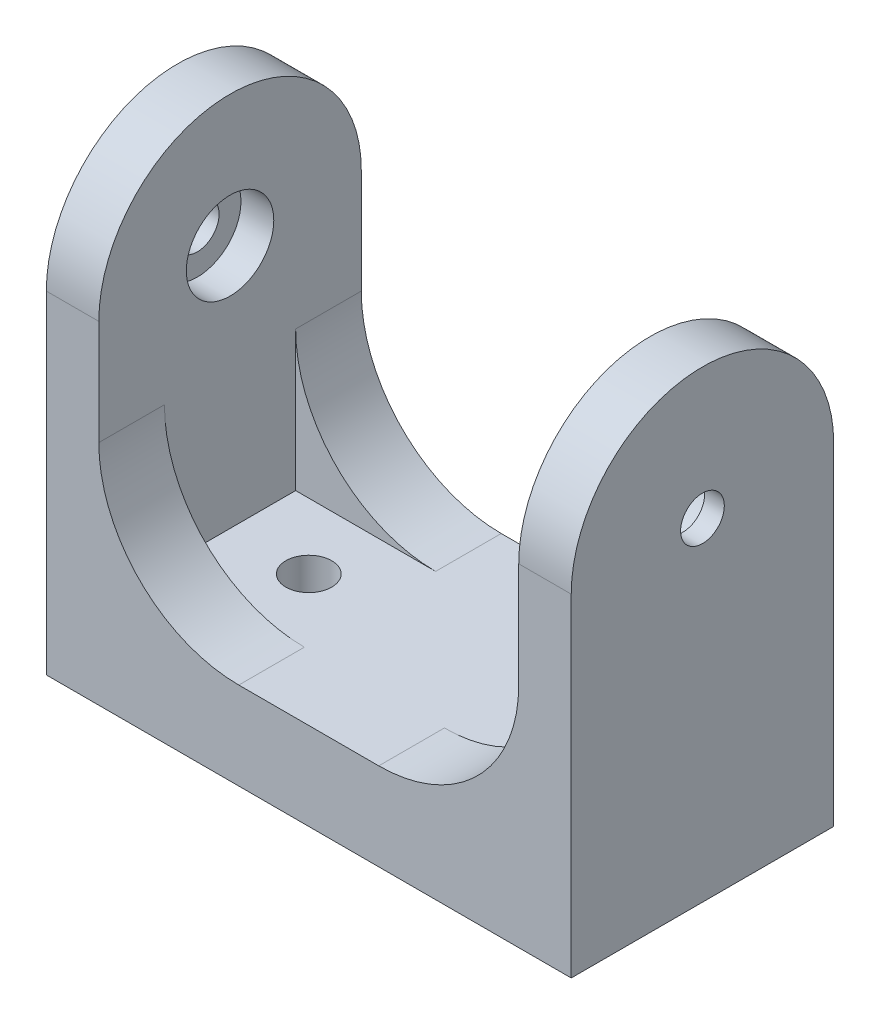
SolidWorks part; units mm, degrees
ref_plane "Front Plane" through (0, 0, 0) normal (0, 0, 1) x (1, 0, 0)
ref_plane "Top Plane" through (0, 0, 0) normal (0, 1, 0) x (1, 0, 0)
ref_plane "Right Plane" through (0, 0, 0) normal (1, 0, 0) x (0, 0, -1)
sketch "Sketch1" plane through (0, 0, 0) normal (0, 1, 0) x (1, 0, 0)
  line L0 (0, 19.05) -> (76.2, 19.05) construction
  line L5 (0, 0) -> (76.2, 0)
  line L6 (0, 0) -> (0, 38.1)
  line L11 (0, 38.1) -> (76.2, 38.1)
  line L12 (76.2, 0) -> (76.2, 38.1)
  line L13 (38.1, 38.1) -> (38.1, 0) construction
  circle A0 centre (19.05, 19.05) radius 3.3274
  circle A1 centre (57.15, 19.05) radius 3.3274
  dimension "D3" = 6.6548
  dimension "D1" = 38.1
  dimension "D2" = 76.2
  dimension "D4" = 19.05
extrude "Boss-Extrude1" add sketch "Sketch1" along normal blind 12.7
ref_plane "Plane2" through (0, 0, 0) normal (-1, 0, 0) x (0, 0, 1)
sketch "Sketch5" plane through (0, 0, 0) normal (-1, 0, 0) x (0, 0, 1)
  line L0 (-38.1, 12.7) -> (0, 12.7)
  line L1 (0, 12.7) -> (0, 48.26)
  line L2 (-38.1, 12.7) -> (-38.1, 48.26)
  arc A0 (0, 48.26) -> (-38.1, 48.26) centre (-19.05, 48.26) ccw
  circle A1 centre (-19.05, 48.26) radius 3.175
  dimension "D2" = 6.35
  dimension "D1" = 35.56
extrude "Boss-Extrude3" add sketch "Sketch5" against normal blind 7.62
fillet "Fillet3" radius 20.32 1 edges at (7.62, 12.7, -19.05)
sketch "Sketch11" plane through (0, 12.7, 0) normal (0, 1, 0) x (1, 0, 0)
  line L0 (7.62, 0) -> (7.62, 38.1) construction
  line L1 (7.62, 28.575) -> (33.02, 28.575)
  line L2 (7.62, 28.575) -> (7.62, 9.525)
  line L3 (7.62, 9.525) -> (33.02, 9.525)
  line L4 (33.02, 28.575) -> (33.02, 9.525)
  line L5 (76.2, 38.1) -> (27.94, 38.1) construction
  dimension "D1" = 25.4
  dimension "D2" = 19.05
  dimension "D3" = 9.525
extrude "Cut-Extrude2" cut sketch "Sketch11" along normal through all
sketch "Sketch13" plane through (7.62, 0, 0) normal (1, 0, 0) x (0, 0, -1)
  circle A0 centre (19.05, 48.26) radius 6.35
  dimension "D1" = 12.7
extrude "Cut-Extrude3" cut sketch "Sketch13" against normal blind 4.7625
ref_plane "Plane3" through (38.1, 0, 0) normal (1, 0, 0) x (0, 0, -1)
mirror "Mirror3" about plane through (38.1, 0, 0) normal (1, 0, 0) of "Fillet3", "Boss-Extrude3"
mirror "Mirror4" about plane through (38.1, 0, 0) normal (1, 0, 0) of "Cut-Extrude2"
mirror "Mirror5" about plane through (38.1, 0, 0) normal (1, 0, 0) of "Cut-Extrude3"
